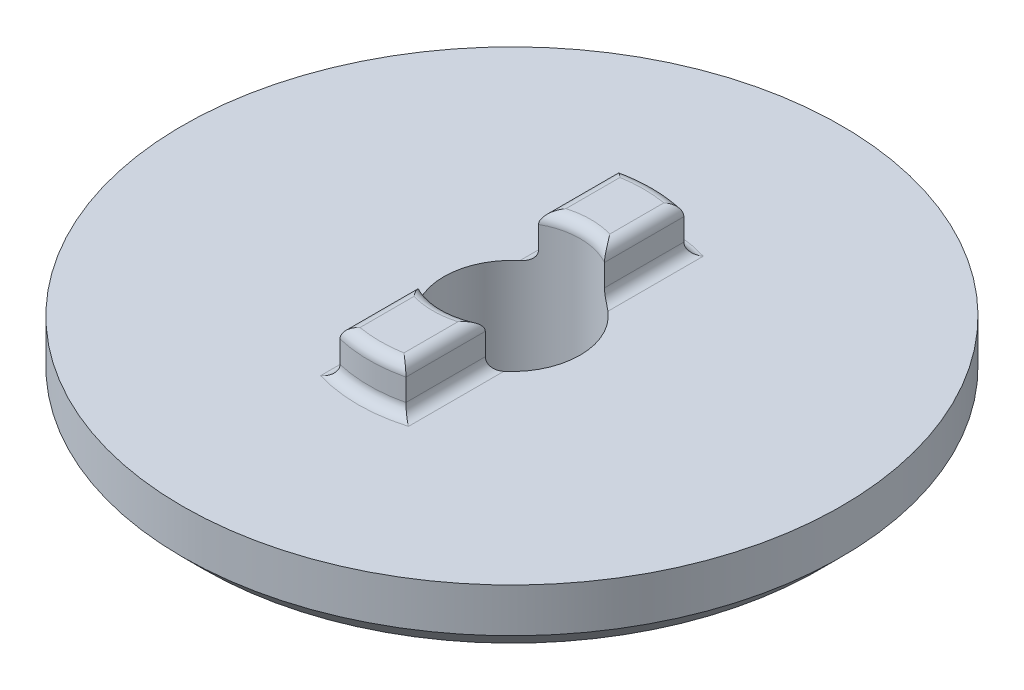
SolidWorks part; units mm, degrees
ref_plane "Спереди" through (0, 0, 0) normal (0, 0, 1) x (1, 0, 0)
ref_plane "Сверху" through (0, 0, 0) normal (0, 1, 0) x (1, 0, 0)
ref_plane "Справа" through (0, 0, 0) normal (1, 0, 0) x (0, 0, -1)
sketch "Эскиз1" plane through (0, 0, 0) normal (0, 1, 0) x (1, 0, 0)
  circle A0 centre (0, 0) radius 15
  circle A1 centre (0, 0) radius 3.1
  dimension "D1" = 30
  dimension "D2" = 6.2
extrude "Бобышка-Вытянуть1" add sketch "Эскиз1" along normal blind 3
sketch "Эскиз2" plane through (0, 3, 0) normal (0, 1, 0) x (1, 0, 0)
  line L1 (1.5, 6.5) -> (-1.5, 6.5)
  line L2 (1.5, 6.5) -> (1.5, -6.5)
  line L3 (1.5, -6.5) -> (-1.5, -6.5)
  line L4 (-1.5, 6.5) -> (-1.5, -6.5)
  line L5 (1.5, 6.5) -> (-1.5, -6.5) construction
  line L6 (1.5, -6.5) -> (-1.5, 6.5) construction
  circle A0 centre (0, 0) radius 6.5
  circle A1 centre (0, 0) radius 3.1
  circle A2 centre (0, 0) radius 3.1 construction
  circle M5 centre (0, 0) radius 3.1
  dimension "D1" = 13
  dimension "D2" = 3
extrude "Бобышка-Вытянуть2" add sketch "Эскиз2" along normal blind 2 contours L2 A0 L4 M5 | A0 L2 L4 M5 region at (0, 3, -4.7066) region at (0, 3, 4.7066)
fillet "Скругление1" radius 0.5 14 edges at (0, 5, -3.1) (-1.5, 5, -4.5187) (0, 5, -6.5) (1.5, 5, -4.5187) (-1.5, 5, 4.5187) (0, 5, 3.1) (1.5, 5, 4.5187) (0, 5, 6.5) (1.5, 3, -4.5187) (-1.5, 3, -4.5187) (0, 3, -6.5) (0, 3, 6.5) (-1.5, 3, 4.5187) (1.5, 3, 4.5187)
sketch "Эскиз3" plane through (0, 0, 0) normal (0, -1, 0) x (1, 0, 0)
  circle A0 centre (0, 0) radius 4.5
  circle A1 centre (0, 0) radius 3.1
  circle A2 centre (0, 0) radius 3.1 construction
  dimension "D1" = 9
extrude "Бобышка-Вытянуть3" add sketch "Эскиз3" along normal blind 5
fillet "Скругление2" radius 1.5 1 edges at (0, 0, 4.5)
chamfer "Фаска1" distance 1 angle 45 1 edges at (0, 0, 15)
